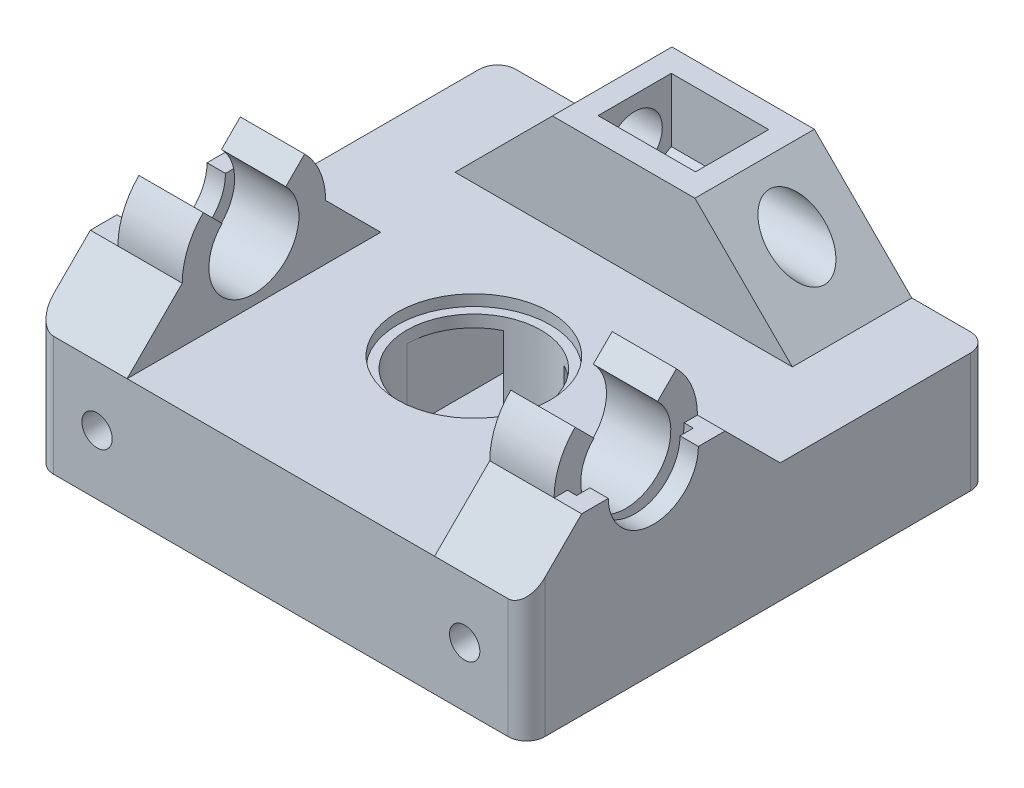
SolidWorks part; units mm, degrees
ref_plane "Front Plane" through (0, 0, 0) normal (0, 0, 1) x (1, 0, 0)
ref_plane "Top Plane" through (0, 0, 0) normal (0, 1, 0) x (1, 0, 0)
ref_plane "Right Plane" through (0, 0, 0) normal (1, 0, 0) x (0, 0, -1)
sketch "Sketch1" plane through (0, 0, 0) normal (0, 0, 1) x (1, 0, 0)
  line L0 (0, 0) -> (0, 74.4848) construction
  line L2 (26.7287, -6.5) -> (-26.7286, -6.5)
  line L3 (26.7287, -6.5) -> (26.7287, 6.5)
  line L4 (26.7287, 6.5) -> (-26.7286, 6.5)
  line L5 (-26.7286, -6.5) -> (-26.7286, 6.5)
  line L6 (26.7287, -6.5) -> (-26.7286, 6.5) construction
  line L7 (26.7287, 6.5) -> (-26.7286, -6.5) construction
  circle A0 centre (-20, 0) radius 4.15
  circle A1 centre (20, 0) radius 4.15
  dimension "D1" = 8.3
  dimension "D2" = 8.3
  dimension "D3" = 20
  dimension "D4" = 20
  dimension "D5" = 53.4573
  dimension "D6" = 13
extrude "Boss-Extrude1" add sketch "Sketch1" along normal blind 50.3
sketch "Sketch3" plane through (0, 0, 50.3) normal (0, 0, 1) x (1, 0, 0)
  circle A0 centre (-20, 0) radius 4.15 construction
  circle A1 centre (20, 0) radius 4.15 construction
  circle A2 centre (-20, 0) radius 4.15
  circle A3 centre (20, 0) radius 4.15
extrude "Boss-Extrude2" add sketch "Sketch3" against normal blind 15
sketch "Sketch5" plane through (-26.7286, 0, 0) normal (-1, 0, 0) x (0, 0, 1)
  line L0 (6.5, 12.5) -> (36.5, 12.5) construction
  line L1 (0, 6.5) -> (0, -6.5) construction
  line L3 (50.3, -6.5) -> (0, -6.5) construction
  circle A0 centre (6.5, 12.5) radius 3
  circle A1 centre (36.5, 12.5) radius 4
  dimension "D1" = 6
  dimension "D2" = 30
  dimension "D3" = 8
  dimension "D4" = 6.5
  dimension "D5" = 19
sketch "Sketch8" plane through (0, 6.5, 0) normal (0, 1, 0) x (1, 0, 0)
  line L0 (-26.7286, -6.5) -> (26.7287, -6.5) construction
  line L1 (-26.7286, -6.5) -> (-26.7286, -36.5) construction
  line L2 (-26.7286, -50.3) -> (-26.7286, 0) construction
  line L3 (26.7287, -50.3) -> (26.7287, 0) construction
  line L4 (26.7287, 0) -> (-26.7286, 0) construction
  line L5 (7.75, -13) -> (-7.75, -13)
  line L6 (7.75, -13) -> (7.75, 0)
  line L7 (7.75, 0) -> (-7.75, 0)
  line L8 (-7.75, -13) -> (-7.75, 0)
  line L9 (7.75, -13) -> (-7.75, 0) construction
  line L10 (7.75, 0) -> (-7.75, -13) construction
  point P8 (0, -6.5)
  dimension "D1" = 15.5
  dimension "D2" = 13
extrude "Boss-Extrude3" add sketch "Sketch8" along normal blind 10.6
chamfer "Chamfer1" distance 10.6 angle 45 2 edges
extrude "Cut-Extrude1" cut sketch "Sketch5" against normal through all
ref_plane "Plane1" through (0, 0, 0) normal (-1, 0, 0) x (0, 0, 1)
sketch "Sketch10" plane through (0, 0, 0) normal (-1, 0, 0) x (0, 0, 1)
  line L0 (2.5163, 14.8) -> (2.5163, 17.1)
  line L1 (10.4837, 10.2) -> (10.4837, 14.8)
  line L4 (2.5163, 14.8) -> (2.5163, 10.2)
  line L5 (2.5163, 10.2) -> (6.5, 7.9)
  line L6 (6.5, 7.9) -> (10.4837, 10.2)
  line L7 (0, 17.1) -> (13, 17.1) construction
  line L8 (2.5163, 17.1) -> (10.4837, 17.1)
  line L9 (10.4837, 17.1) -> (10.4837, 14.8)
  line L11 (6.5, 17.1) -> (2.5163, 14.8) [skipped]
  line L12 (10.4837, 14.8) -> (6.5, 17.1) [skipped]
  arc A0 (2.5163, 14.8) -> (10.4837, 14.8) centre (6.5, 12.5) ccw construction
  dimension "D1" = 9.2
extrude "Cut-Extrude2" cut sketch "Sketch10" against normal blind 5.3
mirror "Mirror1" about plane through (0, 0, 0) normal (-1, 0, 0) of "Cut-Extrude2"
sketch "Sketch11" plane through (-26.7286, 0, 0) normal (-1, 0, 0) x (0, 0, 1)
  line L0 (33.0352, 15.9648) -> (30.9846, 18.0154)
  line L1 (39.9648, 15.9648) -> (42.0154, 18.0154)
  line L2 (28.7, 12.5) -> (22.7, 6.5)
  line L3 (44.3, 12.5) -> (50.3, 6.5)
  line L4 (50.3, 6.5) -> (22.7, 6.5)
  line L15 (50.3, 6.5) -> (0, 6.5) construction
  circle A0 centre (6.5, 12.5) radius 3 construction
  circle A1 centre (6.5, 12.5) radius 3 construction
  arc A2 (33.0352, 15.9648) -> (39.9648, 15.9648) centre (36.5, 12.5) ccw
  arc A3 (30.9846, 18.0154) -> (28.7, 12.5) centre (36.5, 12.5) ccw
  arc A5 (44.3, 12.5) -> (42.0154, 18.0154) centre (36.5, 12.5) ccw
  dimension "D2" = 30
  dimension "D3" = 9.8
  dimension "D4" = 15.6
extrude "Boss-Extrude4" add sketch "Sketch11" against normal blind 10
ref_plane "Plane2" through (-24.7286, 0, 0) normal (-1, 0, 0) x (0, 0, 1)
sketch "Sketch12" plane through (-24.7286, 0, 0) normal (-1, 0, 0) x (0, 0, 1)
  line L0 (30.15, 12.5) -> (30.15, 21.9607)
  line L1 (30.15, 21.9607) -> (42.85, 21.9607)
  line L2 (42.85, 21.9607) -> (42.85, 12.5)
  arc A0 (30.15, 12.5) -> (42.85, 12.5) centre (36.5, 12.5) ccw
  dimension "D1" = 12.7
extrude "Cut-Extrude3" cut sketch "Sketch12" against normal blind 1
sketch "Sketch13" plane through (-26.7286, 0, 0) normal (-1, 0, 0) x (0, 0, 1)
  line L1 (28.7, 12.5) -> (46.3009, 12.5)
  line L2 (28.7, 12.5) -> (28.7, 21.5961)
  line L3 (28.7, 21.5961) -> (46.3009, 21.5961)
  line L4 (46.3009, 12.5) -> (46.3009, 21.5961)
extrude "Cut-Extrude4" cut sketch "Sketch13" against normal blind 3
mirror "Mirror2" about plane through (0, 0, 0) normal (-1, 0, 0) of "Boss-Extrude4", "Cut-Extrude4", "Cut-Extrude3"
sketch "Sketch15" plane through (0, 0, 0) normal (0, 0, -1) x (-1, 0, 0)
  line L0 (-15.85, 0) -> (15.85, 0) construction
  line L1 (0, -10.45) -> (0, 10.45) construction
  line L2 (-3.3, -4) -> (-7.3, -4)
  line L3 (-3.3, -4) -> (-3.3, 4)
  line L4 (-3.3, 4) -> (-7.3, 4)
  line L5 (-7.3, -4) -> (-7.3, 4)
  line L6 (-3.3, -4) -> (-7.3, 4) construction
  line L7 (-3.3, 4) -> (-7.3, -4) construction
  circle A1 centre (-20, 0) radius 4.15 construction
  circle A2 centre (-20, 0) radius 4.15 construction
  circle A3 centre (20, 0) radius 4.15 construction
  point P9 (-5.3, 0)
  dimension "D1" = 4
  dimension "D2" = 8
  dimension "D3" = 3.3
sketch "Sketch16" plane through (0, 6.5, 0) normal (0, 1, 0) x (1, 0, 0)
  line L0 (-16.7286, -36.5) -> (16.7286, -36.5) construction
  line L1 (-16.7286, -22.7) -> (-16.7286, -50.3) construction
  line L2 (16.7286, -22.7) -> (16.7286, -50.3) construction
  line L3 (0, 10.45) -> (0, -10.45) construction
  line L4 (16.7286, -40.5) -> (-16.7286, -40.5) construction
  line L5 (16.7286, -40.5) -> (16.7286, -32.5) construction
  line L6 (16.7286, -32.5) -> (-16.7286, -32.5) construction
  line L7 (-16.7286, -40.5) -> (-16.7286, -32.5) construction
  line L8 (16.7286, -40.5) -> (-16.7286, -32.5) construction
  line L9 (16.7286, -32.5) -> (-16.7286, -40.5) construction
  circle A0 centre (0, -29.3) radius 3.2 construction
  circle A1 centre (0, -29.3) radius 1.65
  point P6 (0, -36.5)
  dimension "D2" = 6.4
  dimension "D3" = 3.3
  dimension "D1" = 8
extrude "Cut-Extrude5" cut sketch "Sketch16" against normal through all
sketch "Sketch17" plane through (0, 6.5, 0) normal (0, 1, 0) x (1, 0, 0)
  circle A0 centre (0, -29.3) radius 7.3
extrude "Cut-Extrude6" cut sketch "Sketch17" against normal blind 10.5
extrude "Cut-Extrude7" cut sketch "Sketch15" against normal up to surface (29.3 mm away) up to face at (-7.3, -4, 29.3)
mirror "Mirror3" about plane through (0, 0, 0) normal (-1, 0, 0) of "Cut-Extrude7"
sketch "Sketch18" plane through (0, 6.5, 0) normal (0, 1, 0) x (1, 0, 0)
  circle A0 centre (0, -29.3) radius 8.3
  dimension "D1" = 16.6
extrude "Cut-Extrude8" cut sketch "Sketch18" against normal blind 1.2
sketch "Sketch20" plane through (0, 0, 0) normal (-1, 0, 0) x (0, 0, 1)
  line L0 (29.3, -4) -> (29.3, 4)
  line L1 (30.95, -4) -> (30.95, -2)
  line L2 (30.95, -2) -> (31.95, -2)
  line L3 (31.95, -2) -> (33.95, -4)
  line L5 (33.95, -4) -> (30.95, -4)
  line L6 (30.95, -4) -> (31.0235, -4.0853)
  dimension "D1" = 2
  dimension "D2" = 1
revolve "Revolve1" add sketch "Sketch20" angle 360 about L0
sketch "Sketch21" plane through (0, 0, 50.3) normal (0, 0, 1) x (1, 0, 0)
  circle A0 centre (20, 0) radius 1.65
  circle A1 centre (-20, 0) radius 1.65
  dimension "D1" = 3.3
  dimension "D2" = 3.3
extrude "Cut-Extrude9" cut sketch "Sketch21" against normal through all
ref_plane "Plane3" through (0, 0, 46.3) normal (0, 0, 1) x (1, 0, 0)
sketch "Sketch22" plane through (0, 0, 46.3) normal (0, 0, 1) x (1, 0, 0)
  line L0 (-22.728, 1.575) -> (-22.728, 3.15)
  line L1 (-22.728, -1.575) -> (-22.728, -7.1772)
  line L2 (-22.728, 1.575) -> (-22.728, -1.575)
  line L5 (-17.272, -1.575) -> (-17.272, 1.575)
  line L6 (-22.728, -7.1772) -> (-17.272, -7.1772)
  line L7 (-22.728, 3.15) -> (-17.272, 3.15)
  line L8 (-17.272, 3.15) -> (-17.272, 1.575)
  line L9 (-17.272, -7.1772) -> (-17.272, -1.575)
  line L10 (-20, 3.15) -> (-22.728, 1.575) [skipped]
  line L11 (-17.272, 1.575) -> (-20, 3.15) [skipped]
  line L13 (-22.728, -1.575) -> (-20, -3.15) [skipped]
  line L14 (-20, -3.15) -> (-17.272, -1.575) [skipped]
  arc A0 (-17.272, -1.575) -> (-22.728, -1.575) centre (-20, 0) ccw construction
  dimension "D1" = 6.3
extrude "Cut-Extrude10" cut sketch "Sketch22" against normal blind 2.4
mirror "Mirror4" about plane through (0, 0, 0) normal (-1, 0, 0) of "Cut-Extrude10"
fillet "Fillet1" radius 2 4 edges at (26.7287, 0, 0) (26.7287, 0, 50.3) (-26.7286, 0, 50.3) (-26.7286, 0, 0)
sketch "Sketch23" plane through (0, 0, 35.3) normal (0, 0, -1) x (-1, 0, 0)
  circle A0 centre (-20, 0) radius 1.65 construction
  circle A1 centre (-20, 0) radius 4.15
  circle A2 centre (-20, 0) radius 4.15
  circle A3 centre (20, 0) radius 4.15
  circle A4 centre (20, 0) radius 4.15
  circle A5 centre (20, 0) radius 1.65 construction
  circle A6 centre (-20, 0) radius 1.65
  circle A7 centre (20, 0) radius 1.65
  dimension "D1" = 0
  dimension "D2" = 0
extrude "Boss-Extrude5" add sketch "Sketch23" along normal blind 5
